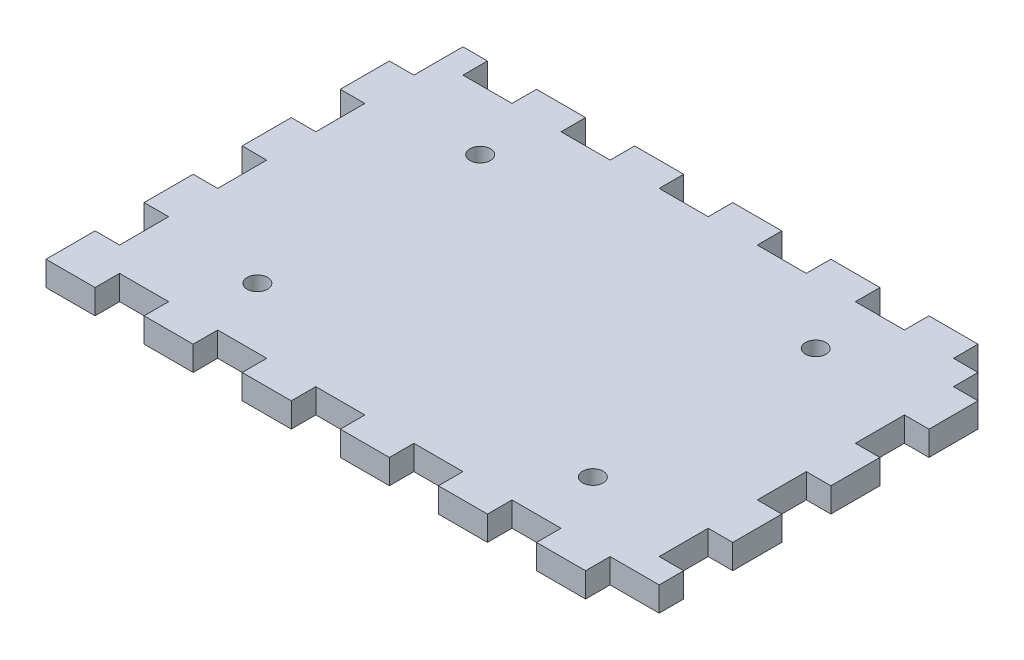
SolidWorks part; units mm, degrees
note: The reader was unsure of these and kept them because the rebuilt part matched: shared geometry of "Sketch2<4>".
material "Cast Alloy Steel"
ref_plane "Front Plane" through (0, 0, 0) normal (0, 0, 1) x (1, 0, 0)
ref_plane "Top Plane" through (0, 0, 0) normal (0, 1, 0) x (1, 0, 0)
ref_plane "Right Plane" through (0, 0, 0) normal (1, 0, 0) x (0, 0, -1)
sketch "Sketch1" plane through (0, 0, 0) normal (0, 1, 0) x (1, 0, 0)
  line L1 (0, 0) -> (152.4, 0)
  line L2 (0, 0) -> (0, 101.6)
  line L3 (0, 101.6) -> (152.4, 101.6)
  line L4 (152.4, 0) -> (152.4, 101.6)
  dimension "D3" = 101.6
  dimension "D5" = 152.4
extrude "Boss-Extrude2" add sketch "Sketch1" along normal blind 6.35
ref_plane "Plane1" through (76.2, 0, 0) normal (-1, 0, 0) x (0, 0, 1)
ref_plane "Plane2" through (0, 0, -50.8) normal (0, 0, -1) x (-1, 0, 0)
sketch "Sketch2" plane through (0, 6.35, 0) normal (0, 1, 0) x (1, 0, 0)
  line L0 (6.35, 101.6) -> (6.35, 0)
  line L1 (12.7, 101.6) -> (12.7, 95.25)
  line L2 (0, 0) -> (152.4, 0) construction
  line L3 (0, 95.25) -> (152.4, 95.25)
  line L4 (25.4, 101.6) -> (25.4, 95.25)
  line L5 (152.4, 0) -> (152.4, 101.6) construction
  line L6 (0, 0) -> (0, 101.6) construction
  line L7 (0, 101.6) -> (152.4, 101.6) construction
  line L8 (0, 12.7) -> (6.35, 12.7)
  line L17 (0, 25.4) -> (6.35, 25.4)
  line L18 (0, 38.1) -> (6.35, 38.1)
  line L19 (0, 50.8) -> (6.35, 50.8)
  line L20 (0, 0) -> (152.4, 0)
  line L21 (152.4, 0) -> (152.4, 101.6)
  line L22 (152.4, 101.6) -> (0, 101.6)
  line L23 (0, 101.6) -> (0, 0)
  line L24 (0, 0) -> (152.4, 0)
  line L25 (152.4, 0) -> (152.4, 101.6)
  line L26 (152.4, 101.6) -> (0, 101.6)
  line L27 (0, 101.6) -> (0, 0)
  line L28 (0, 63.5) -> (6.35, 63.5)
  line L29 (0, 76.2) -> (6.35, 76.2)
  line L30 (0, 88.9) -> (6.35, 88.9)
  line L31 (0, 101.6) -> (6.35, 101.6)
  line L32 (38.1, 101.6) -> (38.1, 95.25)
  line L33 (50.8, 101.6) -> (50.8, 95.25)
  line L34 (63.5, 101.6) -> (63.5, 95.25)
  line L35 (76.2, 101.6) -> (76.2, 95.25)
  line L36 (88.9, 101.6) -> (88.9, 95.25)
  line L37 (101.6, 101.6) -> (101.6, 95.25)
  line L38 (114.3, 101.6) -> (114.3, 95.25)
  line L39 (127, 101.6) -> (127, 95.25)
  line L40 (139.7, 101.6) -> (139.7, 95.25)
  line L41 (152.4, 101.6) -> (152.4, 95.25)
  line L42 (165.1, 101.6) -> (165.1, 95.25)
  dimension "D1" = 6.35
  dimension "D2" = 6.35
  dimension "D4" = 12.7
  dimension "D6" = 12.7
  dimension "D7" = 12.7
  dimension "D5" = 8
extrude "Cut-Extrude2" cut sketch "Sketch2" against normal blind 6.35
mirror "Mirror1" about plane through (76.2, 0, 0) normal (-1, 0, 0) of "Cut-Extrude2"
extrude "Cut-Extrude3" cut sketch "Sketch2<4>" against normal blind 6.35
sketch "Sketch2<4>" plane through (0, 6.35, 0) normal (0, 1, 0) x (1, 0, 0) same geometry as "Sketch2"
mirror "Mirror2" about plane through (0, 0, -50.8) normal (0, 0, -1) of "Cut-Extrude3"
hole_wizard "Ø5.0mm Dowel Hole1" [suppressed] positions "Sketch3" profile "Sketch4" hole size "Ø5.0" standard "ANSI Metric"
sketch "Sketch3" plane through (0, 6.35, 0) normal (0, 1, 0) x (1, 0, 0)
  line L0 (0, 29.526) -> (152.4, 29.526) construction
  line L1 (0, 25.4) -> (0, 38.1) construction
  line L2 (152.4, 25.4) -> (152.4, 38.1) construction
  line L4 (63.5, 6.35) -> (76.2, 6.35) construction
  point P0 (76.2, 31.75)
  point P12 (76.2, 29.526)
  dimension "D1" = 25.4
sketch "Sketch4" plane through (76.2, 6.35, -31.75) normal (1, 0, 0) x (0, 0, 1)
  line L0 (0, 0) -> (0, 6.35)
  line L1 (0, 6.35) -> (2.5, 6.35)
  line L2 (2.5, 6.35) -> (2.5, 0)
  line L5 (2.5, 0) -> (0, 0)
  line L11 (0, -6.35) -> (0, 107.95) construction
  dimension "Thru Hole Dia." = 5
  dimension "Thru Hole Depth" = 6.35
hole_wizard "Ø3.0mm Dowel Hole1" [suppressed] positions "Sketch5" profile "Sketch6" hole size "Ø3.0" standard "ANSI Metric"
sketch "Sketch5" plane through (0, 0, 0) normal (0, -1, 0) x (-1, 0, 0)
  point P0 (-60.7, 47.25)
  point P3 (-91.7, 47.25)
  point P6 (-91.7, 16.25)
  point P9 (-60.7, 16.25)
sketch "Sketch6" plane through (60.7, 0, -47.25) normal (1, 0, 0) x (0, 0, -1)
  line L0 (0, 0) -> (0, 6.35)
  line L1 (0, 6.35) -> (1.5, 6.35)
  line L2 (1.5, 6.35) -> (1.5, 0)
  line L5 (1.5, 0) -> (0, 0)
  line L11 (0, -6.35) -> (0, 107.95) construction
  dimension "Thru Hole Dia." = 3
  dimension "Thru Hole Depth" = 6.35
hole_wizard "Ø5.0mm Dowel Hole2" [suppressed] positions "Sketch7" profile "Sketch8" hole size "Ø5.0" standard "ANSI Metric"
sketch "Sketch7" plane through (0, 6.35, 0) normal (0, 1, 0) x (1, 0, 0)
  line L0 (0, 86.36) -> (152.4, 86.36) construction
  line L1 (0, 76.2) -> (0, 88.9) construction
  line L2 (152.4, 76.2) -> (152.4, 88.9) construction
  line L4 (6.35, 101.6) -> (12.7, 101.6) construction
  point P0 (32.766, 86.36)
  point P17 (119.634, 86.36)
  point P19 (76.2, 86.36)
  dimension "D1" = 12.827
  dimension "D2" = 43.434
  dimension "D3" = 43.434
sketch "Sketch8" plane through (32.766, 6.35, -86.36) normal (1, 0, 0) x (0, 0, 1)
  line L0 (0, 0) -> (0, 6.35)
  line L1 (0, 6.35) -> (2.5, 6.35)
  line L2 (2.5, 6.35) -> (2.5, 0)
  line L5 (2.5, 0) -> (0, 0)
  line L11 (0, -6.35) -> (0, 107.95) construction
  dimension "Thru Hole Dia." = 5
  dimension "Thru Hole Depth" = 6.35
sketch "Sketch9" [suppressed] plane through (0, 6.35, 0) normal (0, 1, 0) x (1, 0, 0)
  line L0 (0, 50.8) -> (152.4, 50.8) construction
  line L1 (17.526, 73.3) -> (48.006, 73.3)
  line L2 (17.526, 73.3) -> (17.526, 28.3)
  line L3 (17.526, 28.3) -> (48.006, 28.3)
  line L4 (48.006, 73.3) -> (48.006, 28.3)
  line L8 (76.2, 0) -> (76.2, 101.6) construction
  line L15 (134.874, 28.3) -> (104.394, 28.3)
  line L16 (104.394, 73.3) -> (104.394, 28.3)
  line L17 (134.874, 73.3) -> (104.394, 73.3)
  line L18 (134.874, 73.3) -> (134.874, 28.3)
  point P8 (32.766, 73.3)
  point P12 (48.006, 50.8)
  point P15 (76.2, 50.8)
  dimension "D2" = 43.434
  dimension "D1" = 25.654
  dimension "D3" = 45
extrude "Cut-Extrude4" [suppressed] cut sketch "Sketch9" against normal through all
sketch "Sketch11" [suppressed] plane through (0, 6.35, 0) normal (0, 1, 0) x (1, 0, 0)
  line L0 (76.2, 88.9) -> (76.2, 57.15) construction
  line L1 (78.7, 88.9) -> (78.7, 57.15)
  line L2 (73.7, 88.9) -> (73.7, 57.15)
  line L3 (76.2, 101.6) -> (76.2, 95.25) construction
  line L5 (76.2, 0) -> (88.9, 0) construction
  arc A0 (78.7, 88.9) -> (73.7, 88.9) centre (76.2, 88.9) ccw
  arc A1 (73.7, 57.15) -> (78.7, 57.15) centre (76.2, 57.15) ccw
  point P2 (76.2, 73.025)
  dimension "D2" = 2.5
  dimension "D1" = 31.75
  dimension "D3" = 57.15
extrude "Cut-Extrude5" [suppressed] cut sketch "Sketch11" against normal through all
sketch "Sketch12" [suppressed] plane through (0, 6.35, 0) normal (0, 1, 0) x (1, 0, 0)
  line L0 (63.5, 6.35) -> (76.2, 6.35) construction
  line L1 (60.325, 19.05) -> (92.075, 19.05)
  line L2 (60.325, 19.05) -> (60.325, 6.35)
  line L3 (60.325, 6.35) -> (92.075, 6.35)
  line L4 (92.075, 19.05) -> (92.075, 6.35)
  line L6 (76.2, 101.6) -> (76.2, 95.25) construction
  point P8 (76.2, 19.05)
  dimension "D1" = 31.75
  dimension "D2" = 12.7
extrude "Cut-Extrude6" [suppressed] cut sketch "Sketch12" against normal through all
hole_wizard "Tap Drill for M3x0.5 Tap1" [suppressed] positions "Sketch16" profile "Sketch17" hole size "M3x0.5" standard "ANSI Metric"
sketch "Sketch16" plane through (0, 6.35, 0) normal (0, 1, 0) x (1, 0, 0)
  line L0 (48.006, 73.3) -> (17.526, 73.3) construction
  line L1 (134.874, 73.3) -> (104.394, 73.3) construction
  line L3 (32.766, 79.65) -> (119.634, 79.65) construction
  line L4 (32.766, 79.65) -> (32.766, 21.95) construction
  line L5 (32.766, 21.95) -> (119.634, 21.95) construction
  line L6 (119.634, 79.65) -> (119.634, 21.95) construction
  line L7 (48.006, 28.3) -> (48.006, 73.3) construction
  point P0 (32.766, 79.65)
  point P2 (32.766, 21.95)
  point P4 (119.634, 21.95)
  point P6 (119.634, 79.65)
  point P11 (32.766, 73.3)
  point P14 (119.634, 73.3)
  point P164 (48.006, 50.8)
  point P165 (32.766, 50.8)
  dimension "D1" = 6.35
sketch "Sketch17" plane through (32.766, 6.35, -79.65) normal (1, 0, 0) x (0, 0, 1)
  line L0 (0, 0) -> (0, 6.35)
  line L1 (0, 6.35) -> (1.25, 6.35)
  line L2 (1.25, 6.35) -> (1.25, 0)
  line L5 (1.25, 0) -> (0, 0)
  line L11 (0, -6.35) -> (0, 107.95) construction
  dimension "Thru Hole Dia." = 2.5
  dimension "Thru Hole Depth" = 6.35
hole_wizard "M5 Clearance Hole2" [suppressed] positions "Sketch20" profile "Sketch21" hole size "M5" standard "ANSI Metric"
sketch "Sketch20" plane through (0, 0, 0) normal (0, -1, 0) x (-1, 0, 0)
  point P0 (-12.7, 76.04)
  point P2 (-12.7, 25.56)
sketch "Sketch21" plane through (12.7, 0, -76.04) normal (1, 0, 0) x (0, 0, -1)
  line L0 (0, 0) -> (0, 6.35)
  line L1 (0, 6.35) -> (2.9, 6.35)
  line L2 (2.9, 6.35) -> (2.9, 0)
  line L5 (2.9, 0) -> (0, 0)
  line L11 (0, -6.35) -> (0, 107.95) construction
  dimension "Thru Hole Dia." = 5.8
  dimension "Thru Hole Depth" = 6.35
hole_wizard "Ø5.0mm Dowel Hole4" [suppressed] positions "Sketch27" profile "Sketch28" hole size "Ø5.0" standard "ANSI Metric"
sketch "Sketch27" plane through (0, 0, 0) normal (0, -1, 0) x (-1, 0, 0)
  line L0 (-152.4, 12.7) -> (0, 12.7) construction
  line L3 (-152.4, 76.2) -> (-152.4, 88.9) construction
  line L4 (0, 76.2) -> (0, 88.9) construction
  line L5 (-127, 0) -> (-139.7, 0) construction
  point P0 (-119.634, 12.7)
  point P2 (-32.766, 12.7)
  point P11 (-76.2, 12.7)
  dimension "D2" = 43.434
  dimension "D3" = 43.434
  dimension "D1" = 12.7
sketch "Sketch28" plane through (119.634, 0, -12.7) normal (1, 0, 0) x (0, 0, -1)
  line L0 (0, 0) -> (0, 6.35)
  line L1 (0, 6.35) -> (2.5, 6.35)
  line L2 (2.5, 6.35) -> (2.5, 0)
  line L5 (2.5, 0) -> (0, 0)
  line L11 (0, -6.35) -> (0, 107.95) construction
  dimension "Thru Hole Dia." = 5
  dimension "Thru Hole Depth" = 6.35
hole_wizard "M5 Clearance Hole3" [suppressed] positions "Sketch29" profile "Sketch30" hole size "M5" standard "ANSI Metric"
sketch "Sketch29" plane through (0, 0, 0) normal (0, -1, 0) x (-1, 0, 0)
  line L0 (-88.9, 95.25) -> (-101.6, 95.25) construction
  point P0 (-95.25, 85.8774)
  point P8 (-95.25, 95.25)
  dimension "D1" = 9.3726
sketch "Sketch30" plane through (95.25, 0, -85.8774) normal (1, 0, 0) x (0, 0, -1)
  line L0 (0, 0) -> (0, 6.35)
  line L1 (0, 6.35) -> (2.75, 6.35)
  line L2 (2.75, 6.35) -> (2.75, 0)
  line L5 (2.75, 0) -> (0, 0)
  line L11 (0, -6.35) -> (0, 107.95) construction
  dimension "Thru Hole Dia." = 5.5
  dimension "Thru Hole Depth" = 6.35
hole_wizard "5/32 (0.15625) Diameter Hole1" [suppressed] positions "Sketch31" profile "Sketch32" hole size "5/32" standard "ANSI Inch"
sketch "Sketch31" plane through (0, 0, 0) normal (0, -1, 0) x (-1, 0, 0)
  line L1 (-66.4845, 28.194) -> (-47.8155, 28.194)
  line L2 (-66.4845, 28.194) -> (-66.4845, 12.7)
  line L3 (-66.4845, 12.7) -> (-47.8155, 12.7)
  line L4 (-47.8155, 28.194) -> (-47.8155, 12.7)
  line L5 (-38.1, 6.35) -> (-50.8, 6.35) construction
  line L6 (-50.8, 0) -> (-63.5, 0) construction
  point P0 (-66.4845, 12.7)
  point P2 (-47.8155, 28.194)
  point P3 (-184.6305, 111.681)
  point P102 (-57.15, 12.7)
  point P105 (-57.15, 0)
  dimension "D1" = 6.35
  dimension "D2" = 18.669
  dimension "D3" = 15.494
sketch "Sketch32" plane through (66.4845, 0, -12.7) normal (1, 0, 0) x (0, 0, -1)
  line L0 (0, 0) -> (0, 6.35)
  line L1 (0, 6.35) -> (1.9844, 6.35)
  line L2 (1.9844, 6.35) -> (1.9844, 0)
  line L5 (1.9844, 0) -> (0, 0)
  line L11 (0, -6.35) -> (0, 107.95) construction
  dimension "Thru Hole Dia." = 3.9688
  dimension "Thru Hole Depth" = 6.35
delete or keep bodies "Body-Delete/Keep 1" [suppressed] type delete bodies bodies 118
sketch "Sketch33" [suppressed] plane through (0, 6.35, 0) normal (0, 1, 0) x (1, 0, 0)
  circle A0 centre (76.2, 31.75) radius 11.049
  circle A1 centre (76.2, 31.75) radius 2.5 construction
  dimension "D1" = 22.098
extrude "Cut-Extrude7" [suppressed] cut sketch "Sketch33" against normal blind 6.35
hole_wizard "Tap Drill for M5x0.8 Tap1" [suppressed] positions "Sketch34" profile "Sketch35" hole size "M5x0.8" standard "ANSI Metric"
sketch "Sketch34" plane through (0, 6.35, 0) normal (0, 1, 0) x (1, 0, 0)
  point P0 (12.7, 76.04)
  point P3 (12.7, 25.56)
sketch "Sketch35" plane through (12.7, 6.35, -76.04) normal (1, 0, 0) x (0, 0, 1)
  line L0 (0, 0) -> (0, 6.35)
  line L1 (0, 6.35) -> (2.1, 6.35)
  line L2 (2.1, 6.35) -> (2.1, 0)
  line L5 (2.1, 0) -> (0, 0)
  line L11 (0, -6.35) -> (0, 107.95) construction
  dimension "Thru Hole Dia." = 4.2
  dimension "Thru Hole Depth" = 6.35
hole_wizard "M3 Clearance Hole1" [suppressed] positions "Sketch36" profile "Sketch37" hole size "M3" standard "ANSI Metric"
sketch "Sketch36" plane through (0, 6.35, 0) normal (0, 1, 0) x (1, 0, 0)
  point P0 (32.766, 79.65)
  point P3 (119.634, 79.65)
  point P6 (119.634, 21.95)
  point P9 (32.766, 21.95)
sketch "Sketch37" plane through (32.766, 6.35, -79.65) normal (1, 0, 0) x (0, 0, 1)
  line L0 (0, 0) -> (0, 6.35)
  line L1 (0, 6.35) -> (1.8, 6.35)
  line L2 (1.8, 6.35) -> (1.8, 0)
  line L5 (1.8, 0) -> (0, 0)
  line L11 (0, -6.35) -> (0, 107.95) construction
  dimension "Thru Hole Dia." = 3.6
  dimension "Thru Hole Depth" = 6.35
hole_wizard "Ø5.0mm Dowel Hole7" positions "Sketch38" profile "Sketch39" hole size "Ø5.0" standard "ANSI Metric" end condition through all
sketch "Sketch38" plane through (0, 0, 0) normal (0, -1, 0) x (-1, 0, 0)
  point P0 (-119.634, 79.65)
  point P3 (-32.766, 79.65)
  point P6 (-32.766, 21.95)
  point P9 (-119.634, 21.95)
sketch "Sketch39" plane through (119.634, 0, -79.65) normal (1, 0, 0) x (0, 0, -1)
  line L0 (0, 0) -> (0, 6.35)
  line L1 (0, 6.35) -> (2.65, 6.35)
  line L2 (2.65, 6.35) -> (2.65, 0)
  line L5 (2.65, 0) -> (0, 0)
  line L11 (0, -6.35) -> (0, 107.95) construction
  dimension "Thru Hole Dia." = 5.3
  dimension "Thru Hole Depth" = 6.35
equation "\"acrillic thickness\"= 1 / 4"
equation "\"D1@Sketch2\"=\"acrillic thickness\""
equation "\"D2@Sketch2\"=\"acrillic thickness\""
equation "\"film hole spacing\"= 0.1866"
equation "\"drive cog diamiter\"= 1.0124"
equation "\"bushing diamiter\"= 1 / 8"
equation "\"D1@Sketch7\"=\"drive cog diamiter\"/2"
equation "\"D1@Sketch9\"=\"drive cog diamiter\""
equation "\"holes between cogs\"= 18"
equation "\"D2@Sketch7\"=\"film hole spacing\"*\"holes between cogs\"/2"
equation "\"D3@Sketch7\"=\"film hole spacing\"*\"holes between cogs\"/2"
equation "\"D2@Sketch9\"=\"film hole spacing\"*\"holes between cogs\"/2"
equation "\"wrench width\"= 0.5 * 2"
equation "\"D1@Sketch12\"=\"wrench width\"*1.25"
equation "\"D2@Sketch27\"=\"holes between cogs\"*\"film hole spacing\"/2"
equation "\"D3@Sketch27\"=\"holes between cogs\"*\"film hole spacing\"/2"
equation "\"Stepper register\"= 0.869in"
equation "\"D1@Sketch33\"=\"Stepper register\""
equation "\"D1@Cut-Extrude7\"=\"acrillic thickness\""
